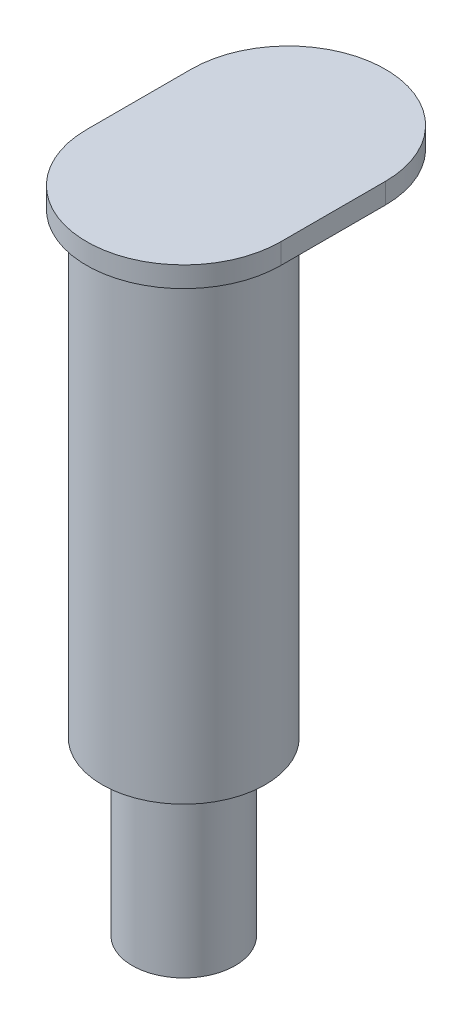
SolidWorks part; units mm, degrees
ref_plane "Front Plane" through (0, 0, 0) normal (0, 0, 1) x (1, 0, 0)
ref_plane "Top Plane" through (0, 0, 0) normal (0, 1, 0) x (1, 0, 0)
ref_plane "Right Plane" through (0, 0, 0) normal (1, 0, 0) x (0, 0, -1)
sketch "Sketch1" plane through (0, 0, 0) normal (0, 1, 0) x (1, 0, 0)
  circle A0 centre (0, 0) radius 15.875
  dimension "D1" = 31.75
extrude "Boss-Extrude1" add sketch "Sketch1" along normal blind 88.9
sketch "Sketch2" plane through (0, 88.9, 0) normal (0, 1, 0) x (1, 0, 0)
  line L0 (0, 0) -> (0, 20.32) construction
  line L1 (-18.875, 0) -> (-18.875, 20.32)
  line L2 (18.875, 0) -> (18.875, 20.32)
  line L3 (0, -18.875) -> (0, 39.195) construction
  arc A0 (-18.875, 0) -> (18.875, 0) centre (0, 0) ccw
  arc A1 (18.875, 20.32) -> (-18.875, 20.32) centre (0, 20.32) ccw
  circle A2 centre (0, 0) radius 15.875 construction
  point P3 (0, 10.16)
  dimension "D1" = 3
  dimension "D2" = 20.32
extrude "Boss-Extrude2" add sketch "Sketch2" along normal blind 4
sketch "Sketch3" plane through (0, 0, 0) normal (0, -1, 0) x (1, 0, 0)
  circle A0 centre (0, 0) radius 10
  dimension "D1" = 20
extrude "Boss-Extrude3" add sketch "Sketch3" along normal blind 33.4
